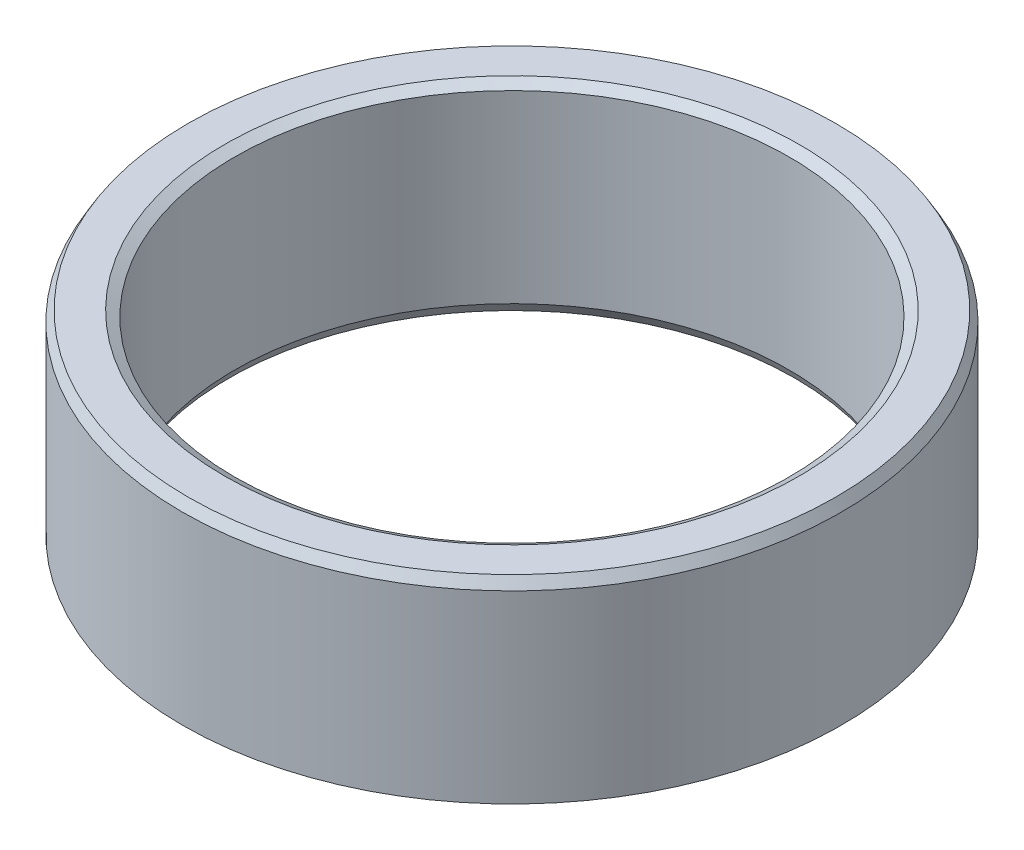
SolidWorks part; units mm, degrees
ref_plane "Front Plane" through (0, 0, 0) normal (0, 0, 1) x (1, 0, 0)
ref_plane "Top Plane" through (0, 0, 0) normal (0, 1, 0) x (1, 0, 0)
ref_plane "Right Plane" through (0, 0, 0) normal (1, 0, 0) x (0, 0, -1)
sketch "Sketch1" plane through (0, 0, 0) normal (0, 1, 0) x (1, 0, 0)
  circle A0 centre (0, 0) radius 32.5
  dimension "SLEEVE_OD" = 65
extrude "Boss-Extrude1" add sketch "Sketch1" along normal blind 19.7615
sketch "Sketch2" plane through (0, 0, 0) normal (0, 1, 0) x (1, 0, 0)
  circle A0 centre (0, 0) radius 27.3422
  dimension "BORE_D" = 54.6843
extrude "Cut-Extrude1" cut sketch "Sketch2" along normal through all
chamfer "Chamfer1" distance 0.9909 angle 30 4 edges at (0, 19.7615, 27.3422) (0, 0, 27.3422) (0, 0, 32.5) (0, 19.7615, 32.5) first distance on face at (0, 19.7615, 27.3422) first distance on face at (0, 0, 27.3422) first distance on face at (0, 19.7615, 32.5)
